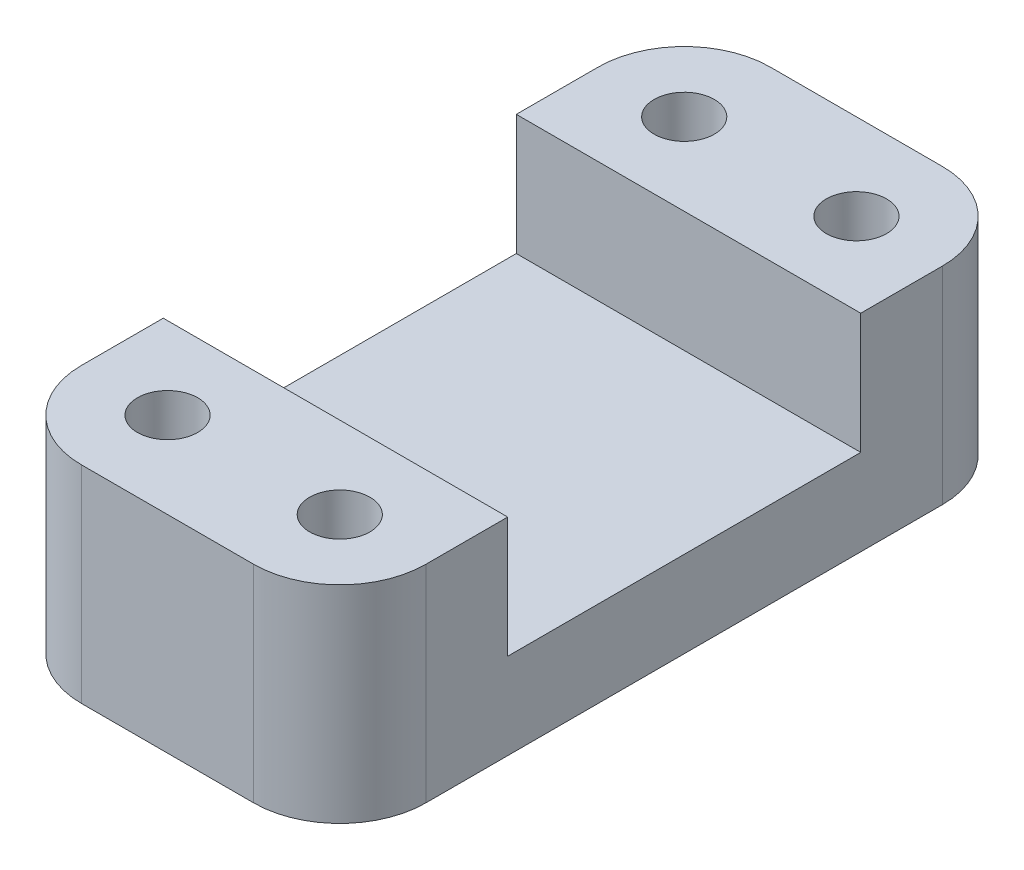
SolidWorks part; units mm, degrees
material "ABS"
ref_plane "Front Plane" through (0, 0, 0) normal (0, 0, 1) x (1, 0, 0)
ref_plane "Top Plane" through (0, 0, 0) normal (0, 1, 0) x (1, 0, 0)
ref_plane "Right Plane" through (0, 0, 0) normal (1, 0, 0) x (0, 0, -1)
sketch "Sketch1" plane through (0, 0, 0) normal (0, 1, 0) x (1, 0, 0)
  line L1 (-10, -20) -> (10, -20)
  line L2 (-10, -20) -> (-10, 20)
  line L3 (-10, 20) -> (10, 20)
  line L4 (10, -20) -> (10, 20)
  line L5 (-10, -20) -> (10, 20) construction
  line L6 (-10, 20) -> (10, -20) construction
  point P0 (0, 0)
  dimension "D1" = 20
  dimension "D2" = 40
extrude "Boss-Extrude1" add sketch "Sketch1" along normal blind 5
sketch "Sketch2" plane through (0, 5, 0) normal (0, 1, 0) x (1, 0, 0)
  line L0 (10, -20) -> (10, 20) construction
  line L1 (-10, -20) -> (10, -20)
  line L2 (-10, -20) -> (-10, -10.25)
  line L3 (-10, -10.25) -> (10, -10.25)
  line L4 (10, -20) -> (10, -10.25)
  line L5 (-10, 20) -> (-10, -20) construction
  line L6 (10, 20) -> (-10, 20)
  line L7 (10, 20) -> (10, 10.25)
  line L8 (10, 10.25) -> (-10, 10.25)
  line L9 (-10, 20) -> (-10, 10.25)
  dimension "D1" = 9.75
  dimension "D2" = 9.75
extrude "Boss-Extrude2" add sketch "Sketch2" along normal blind 7
sketch "Sketch3" plane through (0, 0, 0) normal (0, -1, 0) x (1, 0, 0)
  line L0 (-10, 20) -> (10, 20) construction
  line L1 (10, 20) -> (10, -20) construction
  line L2 (10, -20) -> (-10, -20) construction
  circle A0 centre (5, 15) radius 1.75
  circle A1 centre (-5, 15) radius 1.75
  circle A2 centre (-5, -15) radius 1.75
  circle A3 centre (5, -15) radius 1.75
  dimension "D2" = 3.5
  dimension "D4" = 3.5
  dimension "D6" = 3.5
  dimension "D8" = 3.5
  dimension "D1" = 5
  dimension "D3" = 5
  dimension "D5" = 10
  dimension "D7" = 5
extrude "Cut-Extrude1" cut sketch "Sketch3" against normal through all
hole_wizard "CBORE for M3 Hex Socket Head Cap Screw1" positions "Sketch4" profile "Sketch5" counterbore size "M3" standard "ISO" end condition through all
sketch "Sketch4" plane through (0, 0, 0) normal (0, -1, 0) x (-1, 0, 0)
  point P0 (-5, -15)
  point P3 (5, -15)
  point P6 (5, 15)
  point P9 (-5, 15)
sketch "Sketch5" plane through (5, 0, 15) normal (1, 0, 0) x (0, 0, -1)
  line L0 (0, 0) -> (0, 12)
  line L1 (0, 12) -> (1.7, 12)
  line L3 (1.7, 12) -> (1.7, 3.4)
  line L4 (1.7, 3.4) -> (3.25, 3.4)
  line L5 (3.25, 3.4) -> (3.25, 0)
  line L7 (3.25, 0) -> (0, 0)
  line L11 (0, -6.35) -> (0, 107.95) construction
  dimension "Thru Hole Dia." = 3.4
  dimension "Thru Hole Depth" = 12
  dimension "C'Bore Dia." = 6.5
  dimension "C'Bore Depth" = 3.4
fillet "Fillet1" radius 5 4 edges at (10, 6, -20) (-10, 6, -20) (-10, 6, 20) (10, 6, 20)
